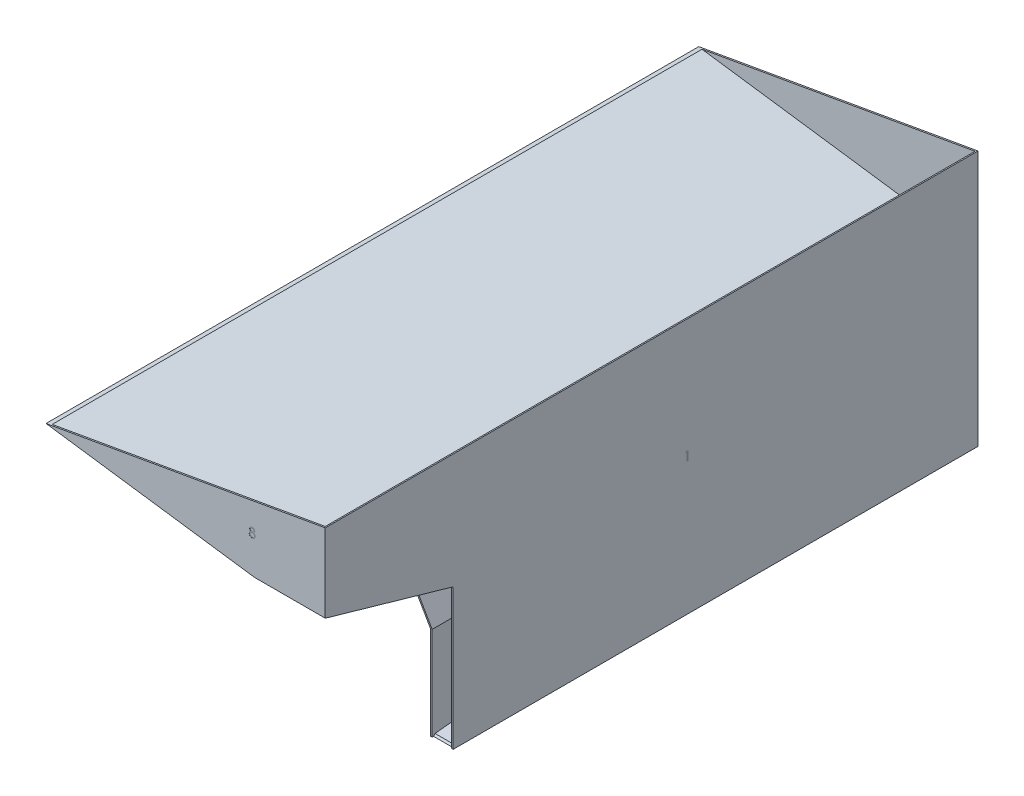
SolidWorks part; units mm, degrees
material "Melamine"
ref_plane "Front Plane" through (0, 0, 0) normal (0, 0, 1) x (1, 0, 0)
ref_plane "Top Plane" through (0, 0, 0) normal (0, 1, 0) x (1, 0, 0)
ref_plane "Right Plane" through (0, 0, 0) normal (1, 0, 0) x (0, 0, -1)
other "Center of Mass"
sketch "Sketch2" plane through (0, 0, 0) normal (0, 0, 1) x (1, 0, 0)
  line L0 (0, 0) -> (-105, 181.8653)
  line L1 (-105, 181.8653) -> (-551.9888, 244.1441)
  line L2 (-551.9888, 244.1441) -> (48.35, 350)
  line L3 (48.35, 350) -> (48.35, -200)
  line L4 (48.35, -200) -> (0, -200)
  line L5 (0, -200) -> (0, 0)
  dimension "D1" = 150
  dimension "D2" = 609.6
  dimension "D3" = 550
  dimension "D4" = 200
  dimension "D5" = 48.35
  dimension "D6" = 210
  dimension "D7" = 280
extrude "Boss-Extrude1" add sketch "Sketch2" along normal mid plane 1403.35
shell "Shell1" thickness 3.175 removed face at (-251.8194, 297.072, 0)
sketch "Sketch3" plane through (0, 0, 701.675) normal (0, 0, 1) x (1, 0, 0)
  line L1 (3.175, -187.3) -> (45.175, -187.3)
  line L2 (3.175, -187.3) -> (3.175, 102.7)
  line L3 (3.175, 102.7) -> (45.175, 102.7)
  line L4 (45.175, -187.3) -> (45.175, 102.7)
  line L6 (0, -200) -> (48.35, -200) construction
  point P6 (24.175, -200)
  point P7 (24.175, -187.3)
  dimension "D1" = 42
  dimension "D2" = 12.7
  dimension "D3" = 290
extrude "Cut-Extrude1" cut sketch "Sketch3" against normal blind 20
sketch "Sketch7" plane through (0, 0, 0) normal (-1, 0, 0) x (0, 0, 1)
  line L1 (701.675, -200) -> (426.675, -200)
  line L2 (701.675, -200) -> (701.675, 102.7)
  line L3 (701.675, 102.7) -> (426.675, 102.7)
  line L4 (426.675, -200) -> (426.675, 102.7)
  dimension "D1" = 275
  dimension "D2" = 302.7
extrude "Cut-Extrude5" cut sketch "Sketch7" against normal mid plane 200
sketch "Sketch9" plane through (48.35, 0, 0) normal (1, 0, 0) x (0, 0, -1)
  line L0 (-701.675, 102.7) -> (-701.675, 350) construction
  line L1 (-426.675, 102.7) -> (-701.675, 102.7)
  line L2 (-426.675, 102.7) -> (-426.675, 181.7)
  line L3 (-426.675, 181.7) -> (-701.675, 181.7)
  line L4 (-701.675, 102.7) -> (-701.675, 181.7)
  line L5 (-701.675, 181.7) -> (-426.675, 102.7)
  line M2 (-701.675, 102.7) -> (-426.675, 102.7)
  line M7 (-701.675, 350) -> (-701.675, 102.7)
  dimension "D1" = 79
extrude "Cut-Extrude7" cut sketch "Sketch9" against normal through all contours L5 M7 M2 region at (48.35, 129.0333, 610.0083)
sketch "Sketch11" plane through (0, -18.3572, 5.2735) normal (0, -0.9611, 0.2761) x (1, 0, 0)
  line L0 (48.35, 724.5674) -> (48.35, 438.445)
  line L1 (48.35, 438.445) -> (-59.2939, 438.445)
  line L2 (-59.2939, 438.445) -> (-104.9045, 724.5674)
  line L3 (-104.9045, 724.5674) -> (48.35, 724.5674)
extrude "Boss-Extrude3" add sketch "Sketch11" against normal blind 6.35
sketch "Sketch12" plane through (3.175, 0, 0) normal (1, 0, 0) x (0, 0, -1)
  line L0 (-426.675, -196.825) -> (688.975, -79.5655)
  line L1 (688.975, -79.5655) -> (688.975, -82.7405)
  line L2 (-396.4669, -196.825) -> (-426.675, -196.825)
  line L3 (701.675, -200) -> (701.675, 350) construction
  line L4 (688.975, -82.7405) -> (-396.4669, -196.825)
  line L5 (-396.4669, -196.825) -> (-396.4669, -193.65)
  line M5 (-426.675, -196.825) -> (698.5, -196.825)
  dimension "D1" = 3.175
  dimension "D2" = 12.7
  dimension "D3" = 6
  dimension "D4" = 3.175
  dimension "D5" = 3.175
extrude "Boss-Extrude4" add sketch "Sketch12" along normal up to surface (42 mm away) contours L5 L4 L1 L0 | L5 L0 M5 region at (3.175, -195.7667, 406.5363) region at (3.175, -138.1952, -146.2541) up to face at (45.175, 100.5897, 182.6102)
chamfer "Chamfer1" distance 6.35 angle 45 1 edges at (24.175, -196.825, 426.675) first distance on face at (24.175, -138.1952, -131.15)
sketch "Sketch14" plane through (48.35, 0, 0) normal (1, 0, 0) x (0, 0, -1)
  line L0 (-426.675, 102.7) -> (-426.675, -200) construction
  line L1 (-426.675, -200) -> (701.675, -200) construction
  text T0 "1" font "Century Gothic" height in points 72
  dimension "D1" = 496.5296
  dimension "D2" = 284.9328
extrude "Cut-Extrude8" cut sketch "Sketch14" against normal blind 0.1
sketch "Sketch15" plane through (0, 0, -701.675) normal (0, 0, -1) x (-1, 0, 0)
  text T0 "2" font "Century Gothic" height in points 72
extrude "Cut-Extrude9" cut sketch "Sketch15" against normal blind 0.1
sketch "Sketch16" plane through (22.8572, 164.0511, 0) normal (-0.138, -0.9904, 0) x (0.9904, -0.138, 0)
  text T0 "3" font "Century Gothic" height in points 72
extrude "Cut-Extrude10" cut sketch "Sketch16" against normal blind 0.1
sketch "Sketch17" plane through (0, 0, 0) normal (-0.866, -0.5, 0) x (0, 0, 1)
  text T0 "4" font "Century Gothic" height in points 72
extrude "Cut-Extrude11" cut sketch "Sketch17" against normal blind 0.1
sketch "Sketch18" plane through (0, 0, 0) normal (-1, 0, 0) x (0, 0, 1)
  text T0 "5" font "Century Gothic" height in points 72
extrude "Cut-Extrude12" cut sketch "Sketch18" against normal blind 0.1
sketch "Sketch19" plane through (0, -200, 0) normal (0, -1, 0) x (1, 0, 0)
  text T0 "6" font "Century Gothic" height in points 72
extrude "Cut-Extrude13" cut sketch "Sketch19" against normal blind 0.1
sketch "Sketch20" plane through (0, -18.3572, 5.2735) normal (0, -0.9611, 0.2761) x (1, 0, 0)
  text T0 "7" font "Century Gothic" height in points 72
extrude "Cut-Extrude14" cut sketch "Sketch20" against normal blind 0.1
sketch "Sketch21" plane through (0, 0, 701.675) normal (0, 0, 1) x (1, 0, 0)
  text T0 "8" font "Century Gothic" height in points 72
extrude "Cut-Extrude15" cut sketch "Sketch21" against normal blind 0.1
